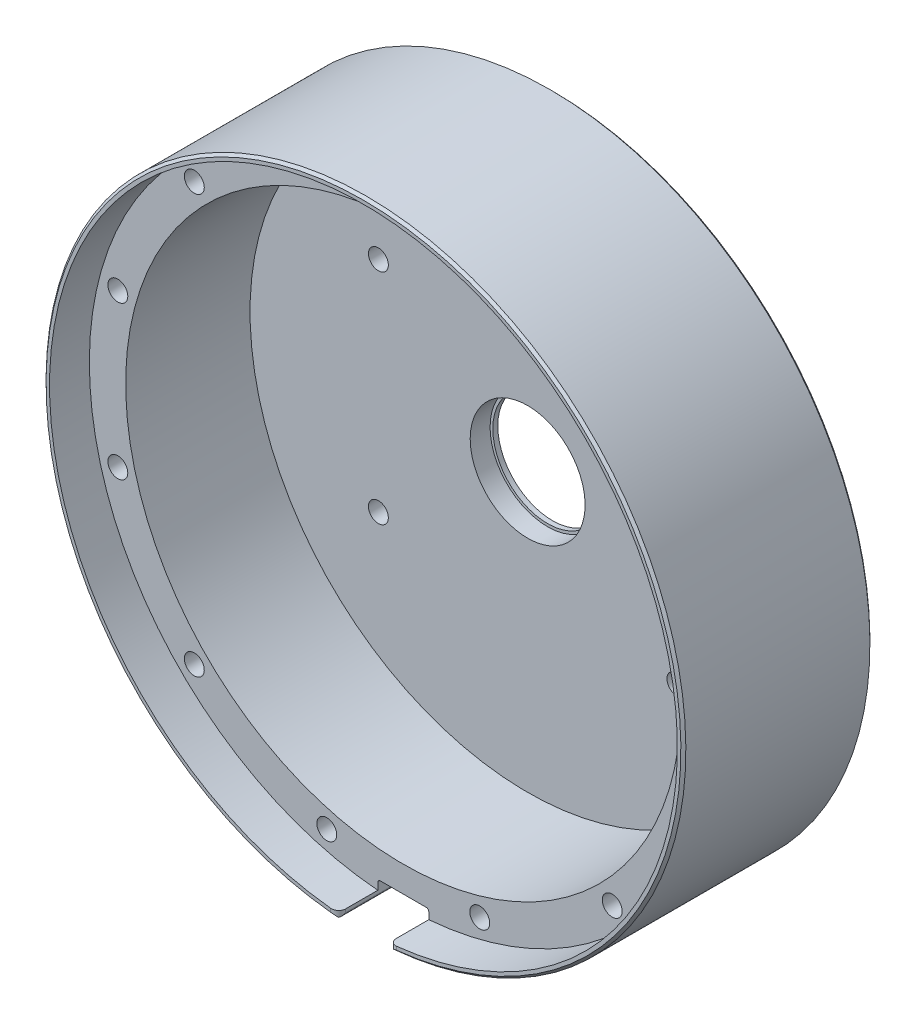
SolidWorks part; units mm, degrees
material "ABS"
ref_plane "Front Plane" through (0, 0, 0) normal (0, 0, 1) x (1, 0, 0)
ref_plane "Top Plane" through (0, 0, 0) normal (0, 1, 0) x (1, 0, 0)
ref_plane "Right Plane" through (0, 0, 0) normal (1, 0, 0) x (0, 0, -1)
sketch "Actuator Housing Mount" plane through (0, 0, 19) normal (0, 0, 1) x (1, 0, 0)
  line L0 (0, 0) -> (63, 0) construction
  line L1 (0, 0) -> (62.0607, 16.6291) construction
  circle A1 centre (57.376, 15.3739) radius 3.6 construction
  circle A2 centre (0, 0) radius 55.8
  circle A3 centre (57.376, 15.3739) radius 1.55
  circle A4 centre (57.376, -15.3739) radius 1.55
  circle A5 centre (42.0021, -42.0021) radius 1.55
  circle A6 centre (15.3739, -57.376) radius 1.55
  circle A7 centre (-15.3739, -57.376) radius 1.55
  circle A8 centre (-42.0021, -42.0021) radius 1.55
  circle A9 centre (-57.376, -15.3739) radius 1.55
  circle A10 centre (-57.376, 15.3739) radius 1.55
  circle A11 centre (-42.0021, 42.0021) radius 1.55
  circle A12 centre (-15.3739, 57.376) radius 1.55
  circle A13 centre (15.3739, 57.376) radius 1.55
  circle A14 centre (42.0021, 42.0021) radius 1.55
  circle A15 centre (0, 0) radius 64.3
  point P35 (0, 0)
extrude "Actuator Housing Wall" add sketch "Actuator Housing Mount" against normal blind 25
sketch "Sketch2" plane through (0, 0, -6) normal (0, 0, -1) x (-1, 0, 0)
  circle A0 centre (0, 0) radius 64.3
  circle A1 centre (0, 0) radius 64.3 construction
  circle M2 centre (-42.0021, 42.0021) radius 1.55
  circle M3 centre (-15.3739, 57.376) radius 1.55
  circle M4 centre (15.3739, 57.376) radius 1.55
  circle M5 centre (42.0021, 42.0021) radius 1.55
  circle M6 centre (57.376, 15.3739) radius 1.55
  circle M7 centre (57.376, -15.3739) radius 1.55
  circle M8 centre (42.0021, -42.0021) radius 1.55
  circle M9 centre (15.3739, -57.376) radius 1.55
  circle M10 centre (-15.3739, -57.376) radius 1.55
  circle M11 centre (-42.0021, -42.0021) radius 1.55
  circle M12 centre (0, 0) radius 55.8
  circle M13 centre (-57.376, -15.3739) radius 1.55
  circle M14 centre (-57.376, 15.3739) radius 1.55
  circle M15 centre (0, 0) radius 64.3
extrude "Boss-Extrude2" add sketch "Sketch2" along normal blind 5 contours M15 M3 M5 M7 M9 M11 M13 M14 M12 M10 M8 M6 M4 M2 | M12
sketch "Sketch3" plane through (0, 0, -11) normal (0, 0, -1) x (-1, 0, 0)
  circle A0 centre (0, 0) radius 11.55
  dimension "D1" = 23.1
extrude "Cut-Extrude1" cut sketch "Sketch3" along normal blind 4 from surface at -5 starting at face at (55.8, 0, -6)
sketch "Sketch4" plane through (0, 0, -11) normal (0, 0, -1) x (-1, 0, 0)
  circle A0 centre (0, 0) radius 11
  dimension "D1" = 22
extrude "Cut-Extrude2" cut sketch "Sketch4" against normal blind 4
sketch "Sketch6" plane through (0, 0, 19) normal (0, 0, 1) x (1, 0, 0)
  circle A0 centre (0, 0) radius 64.3
  circle A1 centre (0, 0) radius 63.1
  dimension "D1" = 128.6
  dimension "D2" = 126.2
extrude "Boss-Extrude3" add sketch "Sketch6" along normal blind 8
sketch "Sketch7" plane through (0, 0, 19) normal (0, 0, 1) x (1, 0, 0)
  circle A0 centre (57.376, -15.3739) radius 2
  circle A1 centre (42.0021, -42.0021) radius 2
  circle A2 centre (15.3739, -57.376) radius 2
  circle A3 centre (-15.3739, -57.376) radius 2
  circle A4 centre (-42.0021, -42.0021) radius 2
  circle A5 centre (-57.376, -15.3739) radius 2
  circle A6 centre (-57.376, 15.3739) radius 2
  circle A7 centre (-42.0021, 42.0021) radius 2
  circle A8 centre (-15.3739, 57.376) radius 2
  circle A9 centre (15.3739, 57.376) radius 2
  circle A10 centre (42.0021, 42.0021) radius 2
  circle A11 centre (57.376, 15.3739) radius 2
  point P27 (0, 0)
  dimension "D1" = 12
  dimension "M3 Insert" = 4
extrude "M3 Insert L12" cut sketch "Sketch7" against normal blind 12
chamfer "Chamfer2" distance 0.5 angle 45 2 edges at (64.3, 0, 27) (-64.3, 0, -11)
sketch "Sketch8" plane through (0, 0, 27) normal (0, 0, 1) x (1, 0, 0)
  line L1 (-5.1219, -61) -> (5.1219, -61)
  line L2 (-5.1219, -61) -> (-5.1219, -65.6855)
  line L3 (-5.1219, -65.6855) -> (5.1219, -65.6855)
  line L4 (5.1219, -61) -> (5.1219, -65.6855)
  dimension "D1" = 10.2438
extrude "Cut-Extrude4" cut sketch "Sketch8" against normal through all
fillet "Fillet2" radius 0.5 2 edges at (-5.1219, -64.0957, 8) (5.1219, -64.0957, 8)
fillet "Fillet3" radius 1.5 2 edges at (5.1219, -63.2218, 27) (-5.1219, -63.2218, 27)
fillet "Fillet5" radius 1.5 1 edges at (0, -61, -11)
fillet "Fillet6" radius 0.5 4 edges at (-5.1223, -63.5729, -11) (5.1223, -63.5729, -11) (-5.1219, -61.5259, -11) (5.1219, -61.5259, -11)
fillet "Fillet7" radius 0.5 6 edges at (-5.1219, -61, 4.75) (-5.1219, -60.9013, -10.0352) (5.1219, -61, 4.75) (5.1219, -60.9013, -10.0352) (-5.292, -60.0979, -10.8757) (5.292, -60.0979, -10.8757)
sketch "Sketch9" plane through (0, 0, -11) normal (0, 0, -1) x (-1, 0, 0)
  line L1 (-30, -22) -> (30, -22) construction
  line L2 (-30, -22) -> (-30, 22) construction
  line L3 (-30, 22) -> (30, 22) construction
  line L4 (30, -22) -> (30, 22) construction
  line L5 (-30, -22) -> (30, 22) construction
  line L6 (-30, 22) -> (30, -22) construction
  circle A0 centre (-30, 22) radius 2
  circle A1 centre (30, 22) radius 2
  circle A2 centre (30, -22) radius 2
  circle A3 centre (-30, -22) radius 2
  point P0 (0, 0)
  dimension "D3" = 4
  dimension "D1" = 60
  dimension "D2" = 44
extrude "Cut-Extrude5" cut sketch "Sketch9" against normal blind 10
